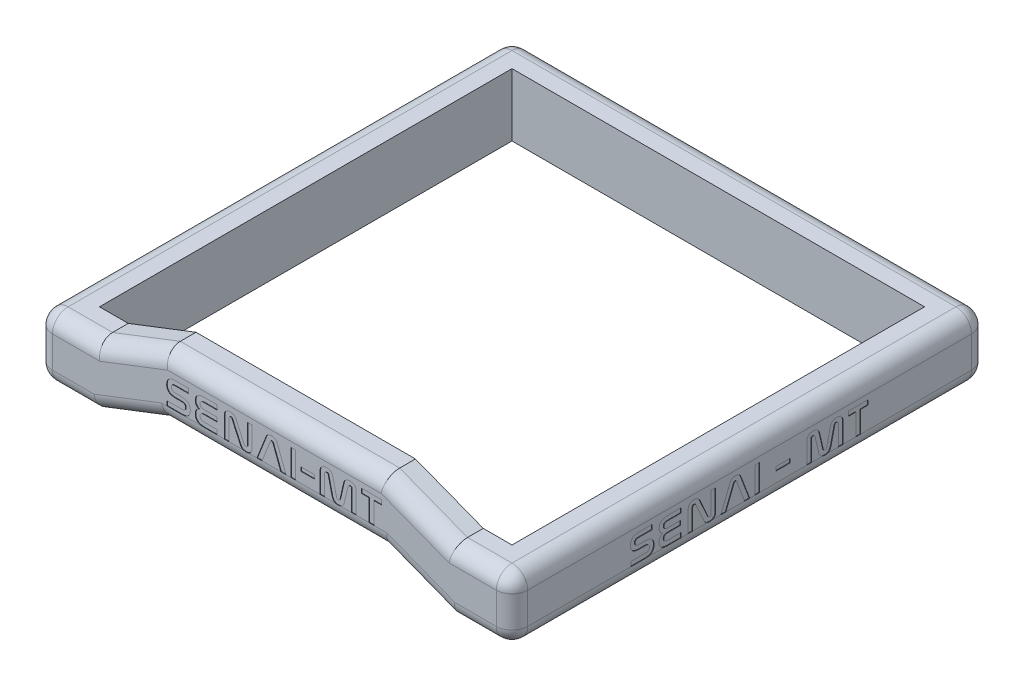
SolidWorks part; units mm, degrees
material "Espuma flexível de poliuretano"
ref_plane "Plano frontal" through (0, 0, 0) normal (0, 0, 1) x (1, 0, 0)
ref_plane "Plano superior" through (0, 0, 0) normal (0, 1, 0) x (1, 0, 0)
ref_plane "Plano direito" through (0, 0, 0) normal (1, 0, 0) x (0, 0, -1)
sketch "Esboço1" plane through (0, 0, 0) normal (0, 0, 1) x (1, 0, 0)
  line L0 (-210, 70) -> (210, 70)
  line L1 (394.8, 19.8) -> (394.8, 139.8)
  line L2 (210, 190) -> (-210, 190)
  line L3 (-394.8, 139.8) -> (-394.8, 19.8)
  line L4 (0, 190) -> (0, 70) construction
  line L5 (0, 70) -> (0, -64.9323) construction
  line L6 (-210, 190) -> (-210, 70) construction
  line L7 (210, 190) -> (210, 70) construction
  line L8 (-394.8, 19.8) -> (394.8, 19.8) construction
  line L9 (-394.8, 19.8) -> (-339.8, 19.8)
  line L10 (-339.8, 19.8) -> (-210, 70)
  line L11 (-394.8, 139.8) -> (-339.8, 139.8)
  line L12 (-339.8, 139.8) -> (-210, 190)
  line L13 (-339.8, 139.8) -> (-339.8, 19.8) construction
  line L14 (394.8, 19.8) -> (339.8, 19.8)
  line L15 (339.8, 19.8) -> (210, 70)
  line L16 (394.8, 139.8) -> (339.8, 139.8)
  line L17 (339.8, 139.8) -> (210, 190)
  line L18 (339.8, 139.8) -> (339.8, 19.8) construction
  line L19 (-385.6567, 0) -> (385.6567, 0) construction
  line L20 (-339.8, 139.8) -> (339.8, 139.8) construction
  line L21 (0, -64.9323) -> (0, 0) construction
  point P17 (0, 0)
  dimension "D1" = 789.6
  dimension "D2" = 420
  dimension "D3" = 394.8
  dimension "D4" = 19.8
  dimension "D5" = 70
  dimension "D6" = 120
  dimension "D7" = 120
  dimension "D8" = 55
  dimension "D9" = 55
  dimension "D10" = 170.2
  dimension "D11" = 190
extrude "Ressalto-extrusão1" add sketch "Esboço1" along normal blind 60
fillet "Filete1" radius 30 10 edges at (367.3, 19.8, 60) (274.9, 44.9, 60) (-367.3, 19.8, 60) (-274.9, 44.9, 60) (0, 70, 60) (367.3, 139.8, 60) (274.9, 164.9, 60) (-367.3, 139.8, 60) (-274.9, 164.9, 60) (0, 190, 60)
sketch "Esboço2" plane through (394.8, 0, 0) normal (1, 0, 0) x (0, 0, -1)
  line L0 (-30, 19.8) -> (0, 19.8) construction
  line L1 (0, 139.8) -> (789.6, 139.8)
  line L3 (0, 19.8) -> (789.6, 19.8)
  line L4 (789.6, 139.8) -> (789.6, 19.8)
  line L5 (-60, 49.8) -> (-60, 109.8) construction
  line L6 (-30, 139.8) -> (0, 139.8) construction
  line L7 (-30, 139.8) -> (0, 139.8)
  line L8 (-60, 49.8) -> (-60, 109.8)
  line L9 (-30, 19.8) -> (0, 19.8)
  line L10 (0, 19.8) -> (0, 139.8) construction
  arc A0 (-30, 139.8) -> (-60, 109.8) centre (-30, 109.8) ccw construction
  arc A1 (-60, 49.8) -> (-30, 19.8) centre (-30, 49.8) ccw construction
  arc A2 (-60, 49.8) -> (-30, 19.8) centre (-30, 49.8) ccw
  arc A3 (-30, 139.8) -> (-60, 109.8) centre (-30, 109.8) ccw
  line M4 (-60, 109.8) -> (-60, 49.8)
  arc M5 (-60, 49.8) -> (-30, 19.8) centre (-30, 49.8) ccw
  line M6 (-30, 19.8) -> (0, 19.8)
  line M7 (0, 19.8) -> (0, 139.8)
  line M8 (0, 139.8) -> (-30, 139.8)
  arc M9 (-30, 139.8) -> (-60, 109.8) centre (-30, 109.8) ccw
  dimension "D1" = 120
  dimension "D2" = 789.6
extrude "Ressalto-extrusão2" add sketch "Esboço2" along normal blind 60 contours L4 L1 L3 M7 | M9 M4 M5 M6 M7 M8 region at (394.8, 79.8, 28.6791) region at (394.8, 79.8, -394.8)
fillet "Filete2" radius 30 5 edges at (454.8, 19.8, -379.8) (454.8, 28.5868, 51.2132) (454.8, 79.8, 60) (454.8, 131.0132, 51.2132) (454.8, 139.8, -379.8)
sketch "Esboço3" plane through (0, 0, -789.6) normal (0, 0, -1) x (-1, 0, 0)
  line L1 (-394.8, 139.8) -> (394.8, 139.8)
  line L3 (-394.8, 19.8) -> (394.8, 19.8)
  line L4 (-454.8, 109.8) -> (-454.8, 49.8)
  line L5 (-424.8, 19.8) -> (-394.8, 19.8)
  line L6 (-394.8, 19.8) -> (-394.8, 139.8)
  line L7 (-394.8, 139.8) -> (-424.8, 139.8)
  line L8 (-454.8, 109.8) -> (-454.8, 49.8)
  line L9 (-424.8, 19.8) -> (-394.8, 19.8)
  line L11 (-394.8, 139.8) -> (-424.8, 139.8)
  line L12 (394.8, 139.8) -> (394.8, 19.8)
  arc A2 (-454.8, 49.8) -> (-424.8, 19.8) centre (-424.8, 49.8) ccw
  arc A3 (-424.8, 139.8) -> (-454.8, 109.8) centre (-424.8, 109.8) ccw
  arc A4 (-454.8, 49.8) -> (-424.8, 19.8) centre (-424.8, 49.8) ccw
  arc A5 (-424.8, 139.8) -> (-454.8, 109.8) centre (-424.8, 109.8) ccw
  dimension "D1" = 0
extrude "Ressalto-extrusão3" add sketch "Esboço3" along normal blind 60
fillet "Filete3" radius 30 5 edges at (15, 19.8, -849.6) (446.0132, 28.5868, -849.6) (454.8, 79.8, -849.6) (446.0132, 131.0132, -849.6) (15, 139.8, -849.6)
sketch "Esboço4" plane through (-394.8, 0, 0) normal (-1, 0, 0) x (0, 0, 1)
  line L1 (-789.6, 139.8) -> (0, 139.8)
  line L3 (-789.6, 19.8) -> (0, 19.8)
  line L4 (-849.6, 109.8) -> (-849.6, 49.8)
  line L5 (-819.6, 19.8) -> (-789.6, 19.8)
  line L6 (-789.6, 19.8) -> (-789.6, 139.8)
  line L7 (-789.6, 139.8) -> (-819.6, 139.8)
  line L8 (-849.6, 109.8) -> (-849.6, 49.8)
  line L9 (-819.6, 19.8) -> (-789.6, 19.8)
  line L11 (-789.6, 139.8) -> (-819.6, 139.8)
  line L12 (0, 19.8) -> (30, 19.8)
  line L13 (60, 49.8) -> (60, 109.8)
  line L14 (30, 139.8) -> (0, 139.8)
  line L15 (0, 139.8) -> (0, 19.8)
  line L16 (0, 19.8) -> (30, 19.8)
  line L17 (60, 49.8) -> (60, 109.8)
  line L18 (30, 139.8) -> (0, 139.8)
  arc A2 (-849.6, 49.8) -> (-819.6, 19.8) centre (-819.6, 49.8) ccw
  arc A3 (-819.6, 139.8) -> (-849.6, 109.8) centre (-819.6, 109.8) ccw
  arc A4 (-849.6, 49.8) -> (-819.6, 19.8) centre (-819.6, 49.8) ccw
  arc A5 (-819.6, 139.8) -> (-849.6, 109.8) centre (-819.6, 109.8) ccw
  arc A6 (30, 19.8) -> (60, 49.8) centre (30, 49.8) ccw
  arc A7 (60, 109.8) -> (30, 139.8) centre (30, 109.8) ccw
  arc A8 (30, 19.8) -> (60, 49.8) centre (30, 49.8) ccw
  arc A9 (60, 109.8) -> (30, 139.8) centre (30, 109.8) ccw
  dimension "D1" = 0
  dimension "D2" = 0
extrude "Ressalto-extrusão4" add sketch "Esboço4" along normal blind 60
fillet "Filete4" radius 30 8 edges at (-454.8, 131.0132, 51.2132) (-454.8, 79.8, 60) (-454.8, 28.5868, 51.2132) (-454.8, 19.8, -394.8) (-454.8, 28.5868, -840.8132) (-454.8, 79.8, -849.6) (-454.8, 131.0132, -840.8132) (-454.8, 139.8, -394.8)
sketch "Esboço5" plane through (454.8, 0, 0) normal (1, 0, 0) x (0, 0, -1)
  text T0 "SENAI - MT" font "Nasalization Rg" height 50
extrude "Corte-extrusão1" cut sketch "Esboço5" against normal blind 1
sketch "Esboço7" plane through (0, 0, -849.6) normal (0, 0, -1) x (-1, 0, 0)
  text T0 "SENAI - MT" font "Nasalization Rg" height 50
extrude "Corte-extrusão2" cut sketch "Esboço7" against normal blind 1
sketch "Esboço8" plane through (-454.8, 0, 0) normal (-1, 0, 0) x (0, 0, 1)
  text T0 "SENAI - MT" font "Nasalization Rg" height 50
extrude "Corte-extrusão3" cut sketch "Esboço8" against normal blind 1
sketch "Esboço9" plane through (0, 0, 60) normal (0, 0, 1) x (1, 0, 0)
  text T0 "SENAI-MT" font "Nasalization Rg" height 50
extrude "Corte-extrusão4" cut sketch "Esboço9" against normal blind 1
